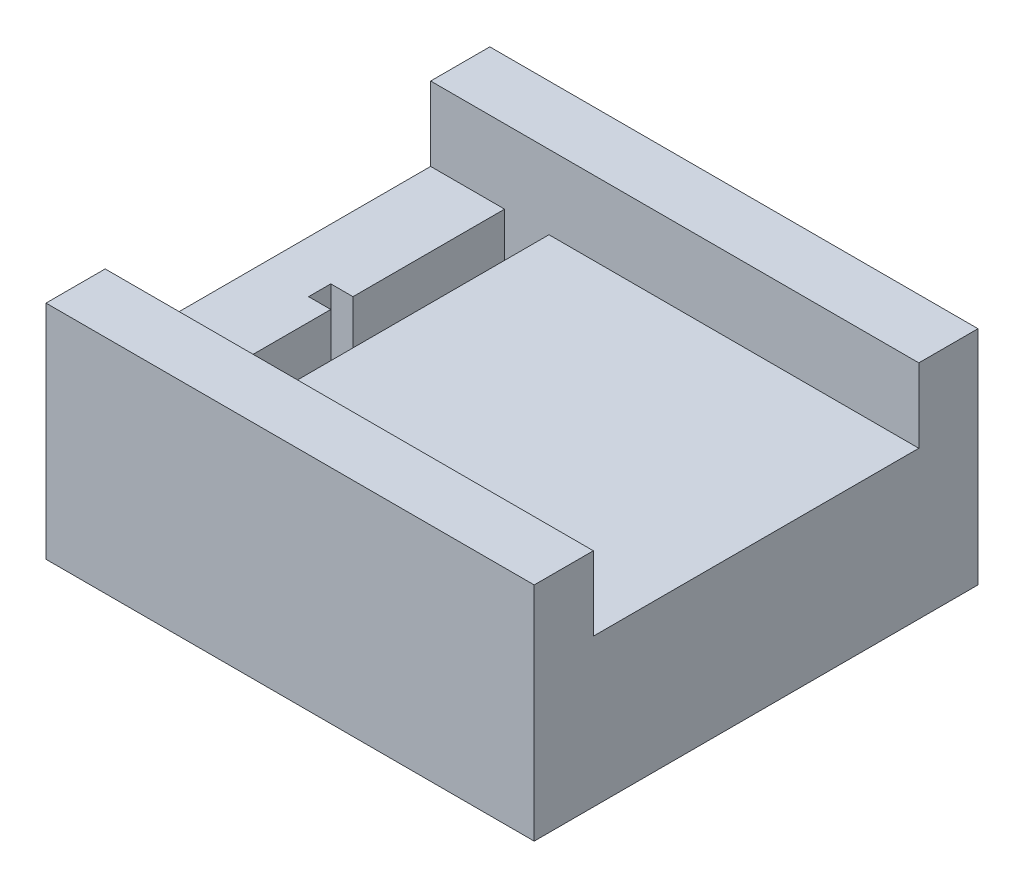
SolidWorks part; units mm, degrees
ref_plane "Front Plane" through (0, 0, 0) normal (0, 0, 1) x (1, 0, 0)
ref_plane "Top Plane" through (0, 0, 0) normal (0, 1, 0) x (1, 0, 0)
ref_plane "Right Plane" through (0, 0, 0) normal (1, 0, 0) x (0, 0, -1)
sketch "Sketch1" plane through (0, 0, 0) normal (0, 1, 0) x (1, 0, 0)
  line L1 (12.5, -11) -> (-12.5, -11)
  line L2 (12.5, -11) -> (12.5, 11)
  line L3 (12.5, 11) -> (-12.5, 11)
  line L4 (-12.5, -11) -> (-12.5, 11)
  line L5 (0, 11) -> (0, -11) construction
  line L6 (12.5, 0) -> (-12.5, 0) construction
  line L7 (-12.5, 11) -> (-15.5, 11)
  line L8 (-12.5, 11) -> (-12.5, -11)
  line L9 (-12.5, -11) -> (-15.5, -11)
  line L10 (-15.5, 11) -> (-15.5, -11)
  line L11 (-15.5, 11) -> (-20.5, 11)
  line L12 (-15.5, 11) -> (-15.5, -11)
  line L13 (-15.5, -11) -> (-20.5, -11)
  line L14 (-20.5, 11) -> (-20.5, -11)
  line L15 (-20.5, -11) -> (12.5, -11)
  line L16 (-20.5, -11) -> (-20.5, -15)
  line L17 (-20.5, -15) -> (12.5, -15)
  line L18 (12.5, -11) -> (12.5, -15)
  line L19 (-20.5, 11) -> (12.5, 11)
  line L20 (-20.5, 11) -> (-20.5, 15)
  line L21 (-20.5, 15) -> (12.5, 15)
  line L22 (12.5, 11) -> (12.5, 15)
  point P0 (0, 0)
  point P13 (0, 0)
  point P14 (0, 0)
  point P15 (0, 0)
  dimension "D1" = 25
  dimension "D2" = 22
  dimension "D3" = 3
  dimension "D4" = 5
  dimension "D5" = 4
  dimension "D6" = 4
extrude "Boss-Extrude3" add sketch "Sketch1" along normal blind 3 contours L7 L10 L9 L4 region at (-14, 0, 0)
extrude "Boss-Extrude4" add sketch "Sketch1<6>" along normal blind 10 contours L4 L1 L2 L3 | L11 L14 L13 L10 region at (0, 0, 0) region at (-18, 0, 0)
sketch "Sketch1<6>" plane through (0, 0, 0) normal (0, 1, 0) x (1, 0, 0) same geometry as "Sketch1"
extrude "Boss-Extrude5" add sketch "Sketch1<7>" along normal blind 15 contours L3 L22 L21 L20 L11 L7 | L18 L1 L9 L13 L16 L17 region at (-4, 0, 13) region at (-4, 0, -13)
sketch "Sketch1<7>" plane through (0, 0, 0) normal (0, 1, 0) x (1, 0, 0) same geometry as "Sketch1"
ref_plane "Plane1" through (0, 10, 0) normal (0, 1, 0) x (1, 0, 0)
sketch "Sketch6" plane through (0, 10, 0) normal (0, 1, 0) x (1, 0, 0)
  line L0 (-15.5, 11) -> (-15.5, -11) construction
  line L1 (-17, 0.75) -> (-15.5, 0.75)
  line L2 (-17, 0.75) -> (-17, -0.75)
  line L3 (-17, -0.75) -> (-15.5, -0.75)
  line L4 (-15.5, 0.75) -> (-15.5, -0.75)
  line L5 (-15.5, 11) -> (-20.5, 11) construction
  line L6 (-15.5, -11) -> (-20.5, -11) construction
  dimension "D1" = 1.5
  dimension "D2" = 1.5
  dimension "D3" = 10.25
  dimension "D4" = 10.25
extrude "Cut-Extrude1" cut sketch "Sketch6" against normal blind 6
